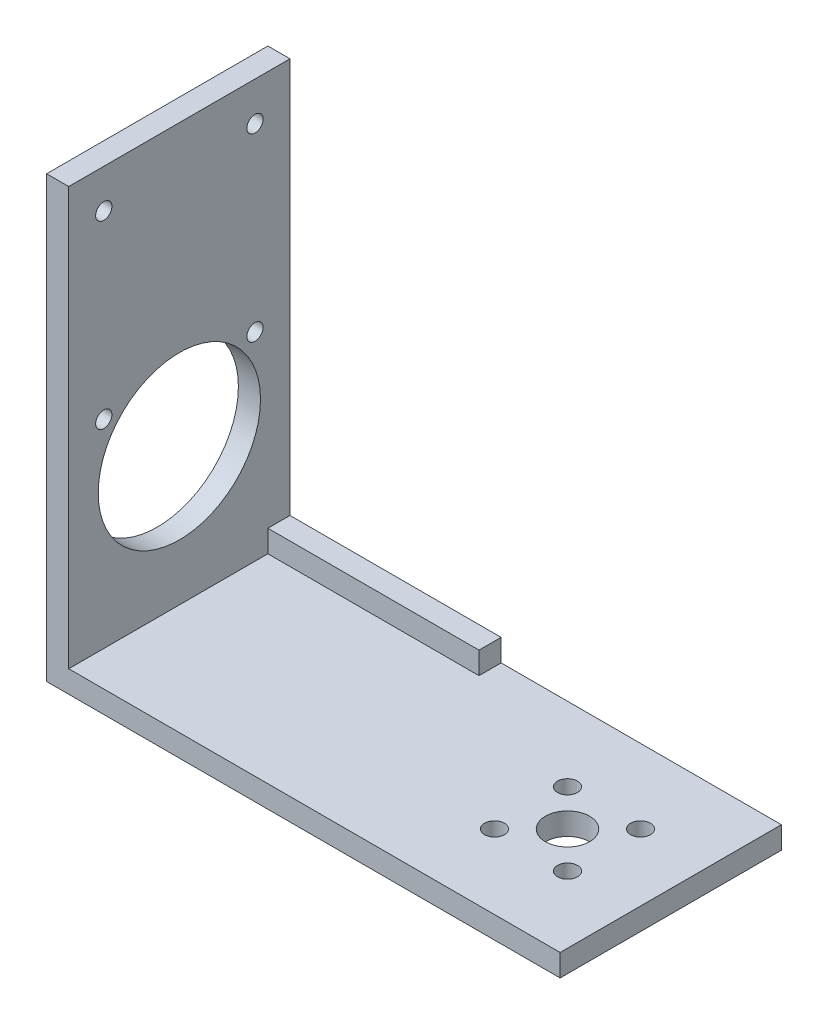
SolidWorks part; units mm, degrees
ref_plane "Front Plane" through (0, 0, 0) normal (0, 0, 1) x (1, 0, 0)
ref_plane "Top Plane" through (0, 0, 0) normal (0, 1, 0) x (1, 0, 0)
ref_plane "Right Plane" through (0, 0, 0) normal (1, 0, 0) x (0, 0, -1)
ref_plane "PZ_m15_000" through (0, 0, -15) normal (0, 0, 1) x (1, 0, 0)
sketch "S_box1" plane through (0, 0, -15) normal (0, 0, 1) x (1, 0, 0)
  line L0 (-55.625, -21.625) -> (14, -21.625)
  line L1 (14, -21.625) -> (14, -18.625)
  line L2 (14, -18.625) -> (-55.625, -18.625)
  line L3 (-55.625, -18.625) -> (-55.625, -21.625)
  dimension "P1" = 55.625
  dimension "P2" = 21.625
  dimension "P3" = 14
  dimension "P4" = 21.625
  dimension "P5" = 14
  dimension "P6" = 18.625
  dimension "P7" = 55.625
  dimension "P8" = 18.625
extrude "Boss_1" add sketch "S_box1" along normal blind 30
sketch "S_box2" plane through (0, 0, -15) normal (0, 0, 1) x (1, 0, 0)
  line L0 (-55.625, -19.125) -> (-52.625, -19.125)
  line L1 (-52.625, -19.125) -> (-52.625, 38)
  line L2 (-52.625, 38) -> (-55.625, 38)
  line L3 (-55.625, 38) -> (-55.625, -19.125)
  dimension "P1" = 55.625
  dimension "P2" = 19.125
  dimension "P3" = 52.625
  dimension "P4" = 19.125
  dimension "P5" = 52.625
  dimension "P6" = 38
  dimension "P7" = 55.625
  dimension "P8" = 38
extrude "Boss_2" add sketch "S_box2" along normal blind 30
sketch "S_box3" plane through (0, 0, -15) normal (0, 0, 1) x (1, 0, 0)
  line L0 (-53.125, -19.125) -> (-24, -19.125)
  line L1 (-24, -19.125) -> (-24, -15.625)
  line L2 (-24, -15.625) -> (-53.125, -15.625)
  line L3 (-53.125, -15.625) -> (-53.125, -19.125)
  dimension "P1" = 53.125
  dimension "P2" = 19.125
  dimension "P3" = 24
  dimension "P4" = 19.125
  dimension "P5" = 24
  dimension "P6" = 15.625
  dimension "P7" = 53.125
  dimension "P8" = 15.625
extrude "Boss_3" add sketch "S_box3" along normal blind 3
ref_plane "PY_m21_725" through (0, -21.725, 0) normal (0, 1, 0) x (1, 0, 0)
sketch "S_hole4" plane through (0, -21.725, 0) normal (0, 1, 0) x (1, 0, 0)
  circle A0 centre (0, 0) radius 3
  dimension "D1_S_hole4" = 6
extrude "Hole_4" cut sketch "S_hole4" along normal blind 3.2
sketch "S_hole5" plane through (0, -21.725, 0) normal (0, 1, 0) x (1, 0, 0)
  circle A0 centre (4.9497, -4.9497) radius 1.35
  dimension "D1_S_hole5" = 2.7
  dimension "P2" = 4.9497
  dimension "P3" = 4.9497
extrude "Hole_5" cut sketch "S_hole5" along normal blind 3.2
sketch "S_hole6" plane through (0, -21.725, 0) normal (0, 1, 0) x (1, 0, 0)
  circle A0 centre (-4.9497, -4.9497) radius 1.35
  dimension "D1_S_hole6" = 2.7
  dimension "P2" = 4.9497
  dimension "P3" = 4.9497
extrude "Hole_6" cut sketch "S_hole6" along normal blind 3.2
sketch "S_hole7" plane through (0, -21.725, 0) normal (0, 1, 0) x (1, 0, 0)
  circle A0 centre (-4.9497, 4.9497) radius 1.35
  dimension "D1_S_hole7" = 2.7
  dimension "P2" = 4.9497
  dimension "P3" = 4.9497
extrude "Hole_7" cut sketch "S_hole7" along normal blind 3.2
sketch "S_hole8" plane through (0, -21.725, 0) normal (0, 1, 0) x (1, 0, 0)
  circle A0 centre (4.9497, 4.9497) radius 1.35
  dimension "D1_S_hole8" = 2.7
  dimension "P2" = 4.9497
  dimension "P3" = 4.9497
extrude "Hole_8" cut sketch "S_hole8" along normal blind 3.2
ref_plane "PX_m55_725" through (-55.725, 0, 0) normal (1, 0, 0) x (0, 0, -1)
sketch "S_hole9" plane through (-55.725, 0, 0) normal (1, 0, 0) x (0, 0, -1)
  circle A0 centre (0, 0) radius 11
  dimension "D1_S_hole9" = 22
extrude "Hole_9" cut sketch "S_hole9" along normal blind 3.2
sketch "S_hole10" plane through (-55.725, 0, 0) normal (1, 0, 0) x (0, 0, -1)
  circle A0 centre (10.25, 8.3) radius 1.1
  dimension "D1_S_hole10" = 2.2
  dimension "P2" = 10.25
  dimension "P3" = 8.3
extrude "Hole_10" cut sketch "S_hole10" along normal blind 3.2
sketch "S_hole11" plane through (-55.725, 0, 0) normal (1, 0, 0) x (0, 0, -1)
  circle A0 centre (-10.25, 8.3) radius 1.1
  dimension "D1_S_hole11" = 2.2
  dimension "P2" = 10.25
  dimension "P3" = 8.3
extrude "Hole_11" cut sketch "S_hole11" along normal blind 3.2
sketch "S_hole12" plane through (-55.725, 0, 0) normal (1, 0, 0) x (0, 0, -1)
  circle A0 centre (10.25, 32.75) radius 1.1
  dimension "D1_S_hole12" = 2.2
  dimension "P2" = 10.25
  dimension "P3" = 32.75
extrude "Hole_12" cut sketch "S_hole12" along normal blind 3.2
sketch "S_hole13" plane through (-55.725, 0, 0) normal (1, 0, 0) x (0, 0, -1)
  circle A0 centre (-10.25, 32.75) radius 1.1
  dimension "D1_S_hole13" = 2.2
  dimension "P2" = 10.25
  dimension "P3" = 32.75
extrude "Hole_13" cut sketch "S_hole13" along normal blind 3.2
equation "\"plate_t\" = 3"
equation "\"clearance\" = 0.4"
